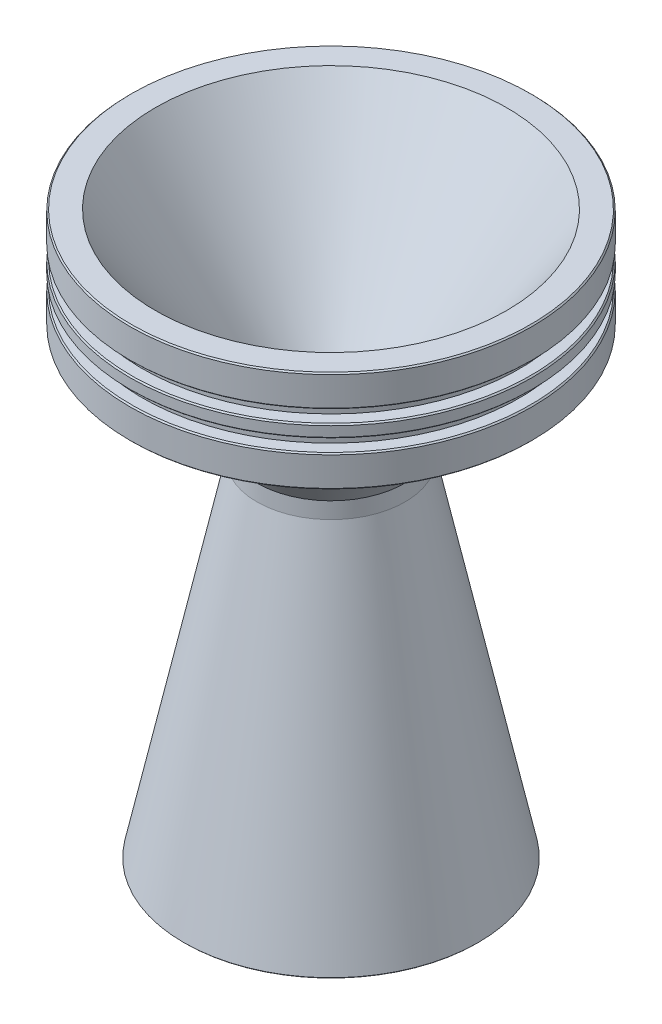
SolidWorks part; units mm, degrees
ref_plane "Front Plane" through (0, 0, 0) normal (0, 0, 1) x (1, 0, 0)
ref_plane "Top Plane" through (0, 0, 0) normal (0, 1, 0) x (1, 0, 0)
ref_plane "Right Plane" through (0, 0, 0) normal (1, 0, 0) x (0, 0, -1)
sketch "Sketch1" plane through (0, 0, 0) normal (0, 0, 1) x (1, 0, 0)
  line L0 (0, 0) -> (2.54, 0)
  line L8 (0, 0) -> (0, -3.175)
  line L9 (0, -3.175) -> (1.27, -3.175)
  line L10 (1.27, -3.175) -> (1.27, -4.445)
  line L11 (1.27, -4.445) -> (0, -4.445)
  line L12 (0, -4.445) -> (0, -5.715)
  line L13 (0, -5.715) -> (1.27, -5.715)
  line L14 (1.27, -5.715) -> (1.27, -6.985)
  line L15 (1.27, -6.985) -> (0, -6.985)
  line L16 (0, -6.985) -> (0, -10.16)
  line L18 (0, 0) -> (20.193, 0) construction
  line L19 (20.193, 0) -> (20.193, -56.515) construction
  line L20 (2.54, 0) -> (16.002, -19.2257)
  line L22 (8.6158, -56.515) -> (5.3699, -56.515)
  line L24 (16.002, -19.2257) -> (16.002, -21.7657)
  line L25 (16.002, -21.7657) -> (8.6158, -56.515)
  line L27 (20.193, -56.515) -> (8.6158, -56.515) construction
  line L29 (5.7781, -10.16) -> (0, -10.16)
  line L30 (12.7561, -21.7657) -> (16.002, -21.7657) construction
  line L33 (12.7561, -20.1255) -> (5.7781, -10.16)
  line L34 (12.7561, -21.7657) -> (5.3699, -56.515)
  line L35 (12.7561, -20.1255) -> (12.7561, -21.7657)
  line L36 (12.7561, -20.1255) -> (16.002, -19.2257) construction
  dimension "D1" = 2.54
  dimension "D2" = 1.27
  dimension "D3" = 1.27
  dimension "D4" = 3.175
  dimension "D5" = 1.27
  dimension "D6" = 20.193
  dimension "D7" = 2.54
  dimension "D8" = 35
  dimension "D9" = 12
  dimension "D10" = 3.175
  dimension "D11" = 4.191
  dimension "D12" = 3.175
  dimension "D13" = 3.175
  dimension "D14" = 56.515
  dimension "D15" = 14.8231
  dimension "D16" = 34.7493
  dimension "D17" = 11.5772
revolve "base_revolve" add sketch "Sketch1" angle 360 about L19
chamfer "outer_chamfers" distance 0.127 angle 45 7 edges at (0, -10.16, 0) (0, 0, 0) (5.3699, -56.515, 0) (0, -5.715, 0) (0, -6.985, 0) (0, -4.445, 0) (0, -3.175, 0) first distance on face at (5.7781, -10.16, 0) first distance on face at (0, -3.175, 0) first distance on face at (8.6158, -56.515, 0) first distance on face at (1.27, -5.715, 0) first distance on face at (0, -6.985, 0) first distance on face at (0, -5.715, 0) first distance on face at (1.27, -3.175, 0)
